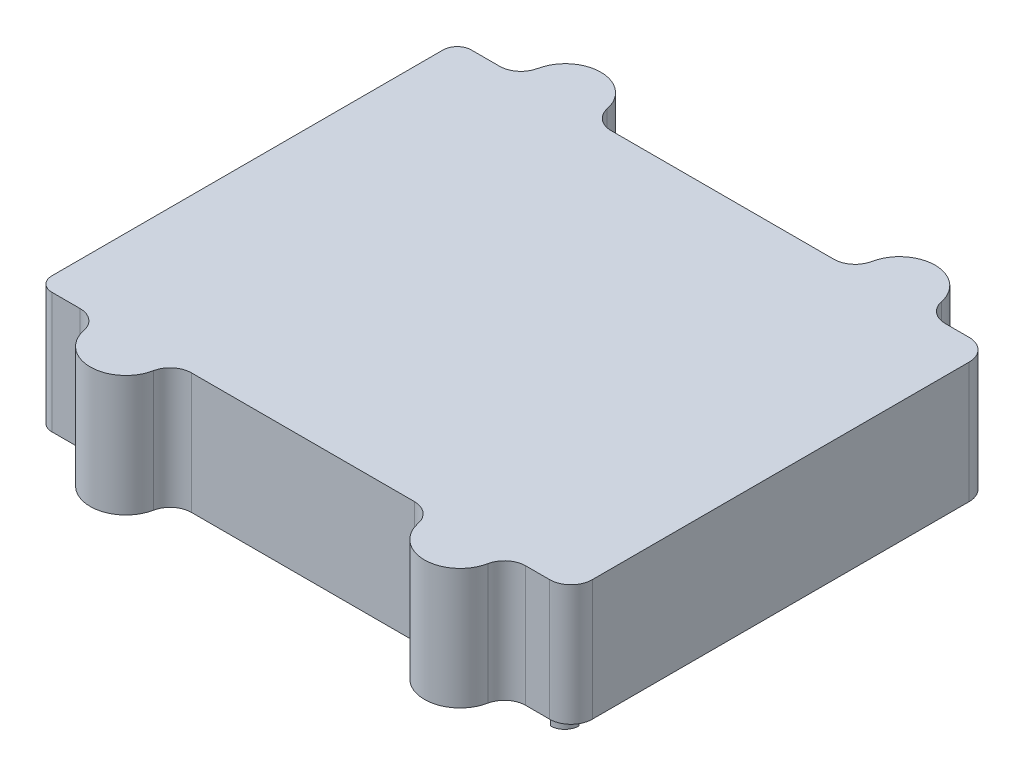
SolidWorks part; units mm, degrees
ref_plane "Front" through (0, 0, 0) normal (0, 0, 1) x (1, 0, 0)
ref_plane "Top" through (0, 0, 0) normal (0, 1, 0) x (1, 0, 0)
ref_plane "Right" through (0, 0, 0) normal (1, 0, 0) x (0, 0, -1)
sketch "Sketch1" plane through (0, 0, 0) normal (0, 1, 0) x (1, 0, 0)
  line L7 (-13.8007, 10.4928) -> (-88.8007, 10.4928)
  line L8 (-13.8007, 10.4928) -> (-13.8007, -48.5072)
  line L9 (-13.8007, -48.5072) -> (-88.8007, -48.5072)
  line L10 (-88.8007, 10.4928) -> (-88.8007, -48.5072)
  line L11 (-51.3007, -48.5072) -> (-51.3007, 10.4928) construction
  line L12 (-13.8007, -19.0072) -> (-88.8007, -19.0072) construction
  dimension "D1" = 75
  dimension "D2" = 59
extrude "Boss-Extrude1" add sketch "Sketch1" along normal blind 17
sketch "Sketch2" plane through (0, 0, 0) normal (0, -1, 0) x (-1, 0, 0)
  line L1 (16.4216, 8.0844) -> (86.452, 8.0844)
  line L2 (16.4216, 8.0844) -> (16.4216, -46.7792)
  line L3 (16.4216, -46.7792) -> (86.452, -46.7792)
  line L4 (86.452, 8.0844) -> (86.452, -46.7792)
extrude "Cut-Extrude1" cut sketch "Sketch2" against normal blind 14.5
fillet "Fillet2" radius 2 1 edges at (-16.4216, 7.25, -8.0844)
fillet "Fillet3" radius 2 1 edges at (-16.4216, 7.25, 46.7792)
fillet "Fillet4" radius 3 1 edges at (-13.8007, 8.5, -10.4928)
fillet "Fillet5" radius 3 1 edges at (-13.8007, 8.5, 48.5072)
fillet "Fillet6" radius 2 1 edges at (-88.8007, 8.5, -10.4928)
fillet "Fillet7" radius 2 1 edges at (-88.8007, 8.5, 48.5072)
sketch "Sketch3" plane through (0, 0, -8.0844) normal (0, 0, 1) x (1, 0, 0)
  line L0 (-18.4216, 0) -> (-18.4216, 14.5) construction
  line L1 (-18.4216, 4.4347) -> (-34.4855, 4.4347)
  line L2 (-18.4216, 4.4347) -> (-18.4216, -2.3261)
  line L3 (-18.4216, -2.3261) -> (-34.4855, -2.3261)
  line L4 (-34.4855, 4.4347) -> (-34.4855, -2.3261)
  line L6 (-69.1538, 4.4347) -> (-86.452, 4.4347)
  line L7 (-69.1538, 4.4347) -> (-69.1538, -2.3261)
  line L8 (-69.1538, -2.3261) -> (-86.452, -2.3261)
  line L9 (-86.452, 4.4347) -> (-86.452, -2.3261)
extrude "Boss-Extrude4" add sketch "Sketch3" along normal blind 1.5 contours L6 L9 L8 L7 | L1 L4 L3 L2
sketch "Sketch4" plane through (0, 0, 46.7792) normal (0, 0, -1) x (-1, 0, 0)
  line L1 (63.1299, 2.7656) -> (47.0768, 2.7656)
  line L2 (63.1299, 2.7656) -> (63.1299, -2.887)
  line L3 (63.1299, -2.887) -> (47.0768, -2.887)
  line L4 (47.0768, 2.7656) -> (47.0768, -2.887)
extrude "Boss-Extrude5" add sketch "Sketch4" along normal blind 1.5 contours L3 L4 L1 L2
sketch "Sketch5" plane through (0, 17, 0) normal (0, 1, 0) x (1, 0, 0)
  line L0 (-16.8007, 10.4928) -> (-86.8007, 10.4928) construction
  line L1 (-86.8007, -48.5072) -> (-16.8007, -48.5072) construction
  circle A0 centre (-75, 11.8928) radius 5
  circle A1 centre (-28, 11.8928) radius 5
  circle A2 centre (-28, -49.9072) radius 5
  circle A3 centre (-75, -49.9072) radius 5
  dimension "D1" = 1.4
  dimension "D2" = 1.4
  dimension "D3" = 1.4
extrude "Boss-Extrude7" add sketch "Sketch5" against normal blind 17 contours A2 | A3 | A1 | A0
fillet "Fillet8" radius 3 1 edges at (-32.8, 8.5, 48.5072)
fillet "Fillet9" radius 3 1 edges at (-23.2, 8.5, 48.5072)
fillet "Fillet10" radius 3 1 edges at (-32.8, 8.5, -10.4928)
fillet "Fillet11" radius 3 1 edges at (-23.2, 8.5, -10.4928)
fillet "Fillet12" radius 3 1 edges at (-70.2, 8.5, -10.4928)
fillet "Fillet13" radius 3 1 edges at (-79.8, 8.5, -10.4928)
fillet "Fillet14" radius 3 1 edges at (-79.8, 8.5, 48.5072)
fillet "Fillet15" radius 3 1 edges at (-70.2, 8.5, 48.5072)
sketch "Sketch6" plane through (0, 14.5, 0) normal (0, -1, 0) x (-1, 0, 0)
  line L0 (42.7345, 8.0844) -> (42.7345, -46.7792)
  line L1 (71.7603, 8.0844) -> (31.2397, 8.0844) construction
  line L2 (31.9008, -46.7792) -> (71.0992, -46.7792) construction
  dimension "D1" = 54.8636
sketch "Sketch7" plane through (0, 0, 0) normal (0, -1, 0) x (-1, 0, 0)
  line L0 (16.4216, -14.7241) -> (86.452, -14.7241)
  line L1 (16.4216, 6.0844) -> (16.4216, -44.7792) construction
  line L2 (86.452, -46.7792) -> (86.452, 8.0844) construction
  dimension "D1" = 70.0304
sketch "Sketch8" plane through (0, 14.5, 0) normal (0, -1, 0) x (-1, 0, 0)
  line L0 (86.452, -46.7792) -> (86.452, 8.0844) construction
  circle A0 centre (70.452, -43.4) radius 3.4
  dimension "D2" = 6.8
  dimension "D1" = 16
extrude "Boss-Extrude8" add sketch "Sketch8" along normal blind 2
sketch "Sketch9" plane through (0, 0, 46.7792) normal (0, 0, -1) x (-1, 0, 0)
  line L1 (67.5222, 12.8026) -> (80.3309, 12.8026)
  line L2 (67.5222, 12.8026) -> (67.5222, 8.3728)
  line L3 (67.5222, 8.3728) -> (80.3309, 8.3728)
  line L4 (80.3309, 12.8026) -> (80.3309, 8.3728)
extrude "Cut-Extrude2" cut sketch "Sketch9" along normal blind 2 contours L3 L4 L1 L2
fillet "Fillet16" radius 2 1 edges at (-75, 8.3728, 44.9072)
sketch "Sketch10" plane through (-86.452, 0, 0) normal (1, 0, 0) x (0, 0, -1)
  line L0 (-46.7792, 14.5) -> (-46.7792, 0) construction
  line L1 (-37.7792, 12.6081) -> (-24.2792, 12.6081)
  line L2 (-37.7792, 12.6081) -> (-37.7792, 0.1081)
  line L3 (-37.7792, 0.1081) -> (-24.2792, 0.1081)
  line L4 (-24.2792, 12.6081) -> (-24.2792, 0.1081)
  dimension "D1" = 12.5
  dimension "D2" = 13.5
  dimension "D3" = 9
extrude "Cut-Extrude3" cut sketch "Sketch10" against normal through all contours L1 L4 L3 L2
sketch "Sketch11" plane through (0, 0, 0) normal (0, -1, 0) x (1, 0, 0)
  line L0 (-86.452, 46.7792) -> (-86.452, -6.5844) construction
  line L1 (-86.452, 22.2083) -> (-88.8007, 22.2083)
  line L2 (-86.452, 22.2083) -> (-86.452, 35.7226)
  line L3 (-86.452, 35.7226) -> (-88.8007, 35.7226)
  line L4 (-88.8007, 22.2083) -> (-88.8007, 35.7226)
  line L5 (-88.8007, -8.4928) -> (-88.8007, 46.5072) construction
sketch "Sketch12" plane through (0, 12.5, 0) normal (0, -1, 0) x (1, 0, 0)
  circle A0 centre (-19.452, 28.34) radius 3.0153
  circle A1 centre (-19.452, 1.24) radius 3.0612
  dimension "D1" = 27.1
extrude "Boss-Extrude9" add sketch "Sketch12" against normal blind 2.5 contours A1 | A0
sketch "Sketch13" plane through (0, 0, 46.7792) normal (0, 0, -1) x (-1, 0, 0)
  line L0 (31.9008, 14.5) -> (70.0768, 14.5) construction
  line L1 (35.6489, 14.5) -> (21.4168, 14.5)
  line L2 (35.6489, 14.5) -> (35.6489, 7.9029)
  line L3 (35.6489, 7.9029) -> (21.4168, 7.9029)
  line L4 (21.4168, 14.5) -> (21.4168, 7.9029)
extrude "Cut-Extrude5" cut sketch "Sketch13" along normal blind 2 contours L3 L4 L1 L2
sketch "Sketch14" plane through (0, 0, -8.0844) normal (0, 0, 1) x (1, 0, 0)
  line L0 (-71.7603, 14.5) -> (-31.2397, 14.5) construction
  line L1 (-23.2344, 7.1575) -> (-33.4413, 7.1575)
  line L2 (-23.2344, 7.1575) -> (-23.2344, 14.5)
  line L3 (-23.2344, 14.5) -> (-33.4413, 14.5)
  line L4 (-33.4413, 7.1575) -> (-33.4413, 14.5)
extrude "Cut-Extrude6" cut sketch "Sketch14" along normal blind 2 contours L2 L3 L4 L1
sketch "Sketch15" plane through (0, 0, -8.0844) normal (0, 0, 1) x (1, 0, 0)
  line L0 (-86.452, 14.5) -> (-78.2397, 14.5) construction
  line L1 (-69.8022, 9.8755) -> (-81.1042, 9.8755)
  line L2 (-69.8022, 9.8755) -> (-69.8022, 14.5)
  line L3 (-69.8022, 14.5) -> (-81.1042, 14.5)
  line L4 (-81.1042, 9.8755) -> (-81.1042, 14.5)
extrude "Cut-Extrude7" cut sketch "Sketch15" along normal blind 2 contours L1 L4 L3 L2
sketch "Sketch17" plane through (-86.452, 0, 0) normal (1, 0, 0) x (0, 0, -1)
  line L0 (-46.7792, 0) -> (6.5844, 0) construction
  line L1 (5.3973, 0) -> (-7.0425, 0)
  line L2 (5.3973, 0) -> (5.3973, 13.0144)
  line L3 (5.3973, 13.0144) -> (-7.0425, 13.0144)
  line L4 (-7.0425, 0) -> (-7.0425, 13.0144)
extrude "Cut-Extrude8" cut sketch "Sketch17" against normal blind 0.8 contours L2 L3 L4 L1
sketch "Sketch19" plane through (0, 14.5, 0) normal (0, -1, 0) x (-1, 0, 0)
  line L1 (77.4659, -37.5353) -> (75.1989, -37.5353)
  line L2 (77.4659, -37.5353) -> (77.4659, -24.0939)
  line L3 (77.4659, -24.0939) -> (75.1989, -24.0939)
  line L4 (75.1989, -37.5353) -> (75.1989, -24.0939)
  point P4 (75.4264, -24.3128)
  point P5 (82.9062, -40.9063)
sketch "Sketch20" plane through (0, 0, 0) normal (0, -1, 0) x (1, 0, 0)
  line L0 (-88.8007, -8.4928) -> (-88.8007, 46.5072) construction
  line L1 (-88.8007, 37.7491) -> (-86.4457, 37.7491)
  line L2 (-88.8007, 37.7491) -> (-88.8007, 24.2894)
  line L3 (-88.8007, 24.2894) -> (-86.4457, 24.2894)
  line L4 (-86.4457, 37.7491) -> (-86.4457, 24.2894)
extrude "Cut-Extrude9" cut sketch "Sketch20" against normal blind 10 contours L1 L4 L3 L2
sketch "Sketch24" plane through (0, 0, 45.2792) normal (0, 0, -1) x (-1, 0, 0)
  line L1 (63.1299, -2.887) -> (47.0768, -2.887)
  line L2 (63.1299, -2.887) -> (63.1299, 2.7656)
  line L3 (63.1299, 2.7656) -> (47.0768, 2.7656)
  line L4 (47.0768, -2.887) -> (47.0768, 2.7656)
extrude "Cut-Extrude10" cut sketch "Sketch24" against normal blind 1.5
sketch "Sketch25" plane through (0, 0, -6.5844) normal (0, 0, 1) x (1, 0, 0)
  line L1 (-69.1538, -2.3261) -> (-86.452, -2.3261)
  line L2 (-69.1538, -2.3261) -> (-69.1538, 4.4347)
  line L3 (-69.1538, 4.4347) -> (-86.452, 4.4347)
  line L4 (-86.452, -2.3261) -> (-86.452, 4.4347)
extrude "Cut-Extrude11" cut sketch "Sketch25" against normal blind 1.5 contours L1 L4 L3 L2
sketch "Sketch26" plane through (0, 0, -6.5844) normal (0, 0, 1) x (1, 0, 0)
  line L0 (-18.4216, 4.4347) -> (-34.4855, 4.4347) construction
  line L1 (-18.4216, -2.3261) -> (-34.4855, -2.3261)
  line L2 (-18.4216, -2.3261) -> (-18.4216, 4.4347)
  line L3 (-18.4216, 4.4347) -> (-34.4855, 4.4347)
  line L4 (-34.4855, -2.3261) -> (-34.4855, 4.4347)
extrude "Cut-Extrude12" cut sketch "Sketch26" against normal blind 1.5 contours L1 L4 L3 L2
sketch "Sketch27" plane through (0, 0, -8.0844) normal (0, 0, 1) x (1, 0, 0)
  line L1 (-23.1216, 3.3099) -> (-33.3667, 3.3099)
  line L2 (-23.1216, 3.3099) -> (-23.1216, 8.7148)
  line L3 (-23.1216, 8.7148) -> (-33.3667, 8.7148)
  line L4 (-33.3667, 3.3099) -> (-33.3667, 8.7148)
  line L5 (-70.2187, 3.7481) -> (-79.1644, 3.7481)
  line L6 (-70.2187, 3.7481) -> (-70.2187, 10.8128)
  line L7 (-70.2187, 10.8128) -> (-79.1644, 10.8128)
  line L8 (-79.1644, 3.7481) -> (-79.1644, 10.8128)
extrude "Cut-Extrude15" cut sketch "Sketch27" along normal blind 1.5 contours L5 L8 L7 L6 | L1 L4 L3 L2
sketch "Sketch29" plane through (0, 0, 46.7792) normal (0, 0, -1) x (-1, 0, 0)
  line L1 (82.2429, 8.9599) -> (22.572, 8.9599)
  line L2 (82.2429, 8.9599) -> (82.2429, -0.8649)
  line L3 (82.2429, -0.8649) -> (22.572, -0.8649)
  line L4 (22.572, 8.9599) -> (22.572, -0.8649)
extrude "Cut-Extrude23" cut sketch "Sketch29" along normal blind 2.5 contours L2 L3 L4 L1
sketch "Sketch30" plane through (-86.452, 0, 0) normal (1, 0, 0) x (0, 0, -1)
  line L0 (8.0844, 14.5) -> (8.0844, 0) construction
  line L1 (8.0844, 1.9321) -> (5.5, 1.9321)
  line L2 (8.0844, 1.9321) -> (8.0844, -1.673)
  line L3 (8.0844, -1.673) -> (5.5, -1.673)
  line L4 (5.5, 1.9321) -> (5.5, -1.673)
  line L5 (-46.7792, 14.5) -> (-46.7792, 0) construction
  line L6 (-46.7792, 1.9321) -> (-43.55, 1.9321)
  line L7 (-46.7792, 1.9321) -> (-46.7792, -1.673)
  line L8 (-46.7792, -1.673) -> (-43.55, -1.673)
  line L9 (-43.55, 1.9321) -> (-43.55, -1.673)
  point P12 (0, 0)
  point P13 (0, 0)
  point P14 (0, 0)
  point P15 (0, 0)
extrude "Boss-Extrude10" add sketch "Sketch30" along normal blind 1.5 contours L9 L8 L7 L6 | L2 L3 L4 L1
sketch "Sketch33" plane through (0, 14.5, 0) normal (0, -1, 0) x (1, 0, 0)
  line L0 (-18.4216, 46.7792) -> (-18.4216, 44.7792)
  line L1 (-18.4216, 44.7792) -> (-16.4216, 44.7792)
  arc A0 (-16.4216, 44.7792) -> (-18.4216, 46.7792) centre (-18.4216, 44.7792) ccw
extrude "Boss-Extrude12" add sketch "Sketch33" along normal blind 17 contours L0 L1 A0
sketch "Sketch34" plane through (0, 14.5, 0) normal (0, -1, 0) x (-1, 0, 0)
  line L0 (16.4216, 6.0844) -> (18.4216, 6.0844)
  line L1 (18.4216, 6.0844) -> (18.4216, 8.0844)
  arc A0 (16.4216, 6.0844) -> (18.4216, 8.0844) centre (18.4216, 6.0844) cw
extrude "Boss-Extrude13" add sketch "Sketch34" along normal blind 17 contours L0 L1 A0
fillet "Fillet25" radius 1 1 edges at (-18.4216, 6, -6.0844)
fillet "Fillet26" radius 1 1 edges at (-18.4216, 6, 44.7792)
